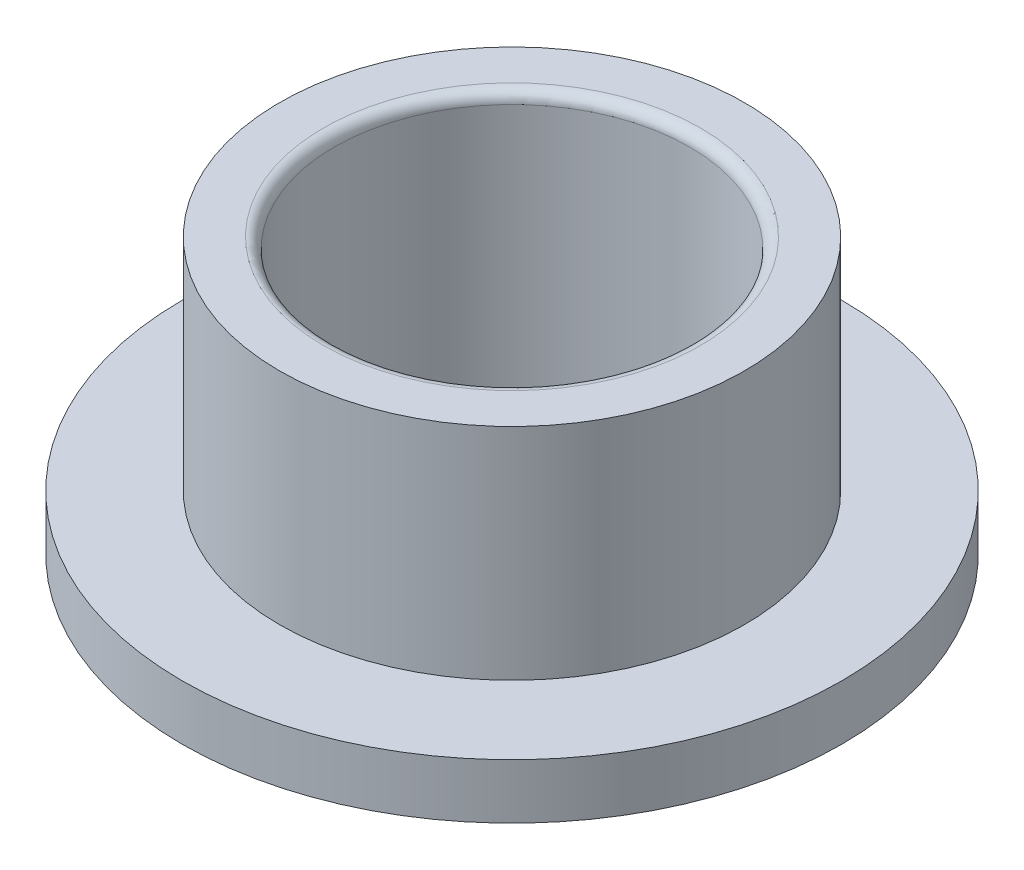
SolidWorks part; units mm, degrees
ref_plane "Front Plane" through (0, 0, 0) normal (0, 0, 1) x (1, 0, 0)
ref_plane "Top Plane" through (0, 0, 0) normal (0, 1, 0) x (1, 0, 0)
ref_plane "Right Plane" through (0, 0, 0) normal (1, 0, 0) x (0, 0, -1)
sketch "Sketch1" plane through (0, 0, 0) normal (0, 1, 0) x (1, 0, 0)
  circle A0 centre (0, 0) radius 16.15
  circle A1 centre (0, 0) radius 21.15
  dimension "D1" = 32.3
  dimension "D2" = 5
extrude "Boss-Extrude1" add sketch "Sketch1" along normal blind 20
fillet "Fillet1" radius 1 1 edges at (0, 20, 16.15)
sketch "Sketch2" plane through (0, 0, 0) normal (0, -1, 0) x (1, 0, 0)
  circle A0 centre (0, 0) radius 16.15 construction
  circle A1 centre (0, 0) radius 16.15
  circle A2 centre (0, 0) radius 30
  dimension "D1" = 60
extrude "Boss-Extrude2" add sketch "Sketch2" along normal blind 5
fillet "Fillet2" radius 1 1 edges at (0, -5, -16.15)
